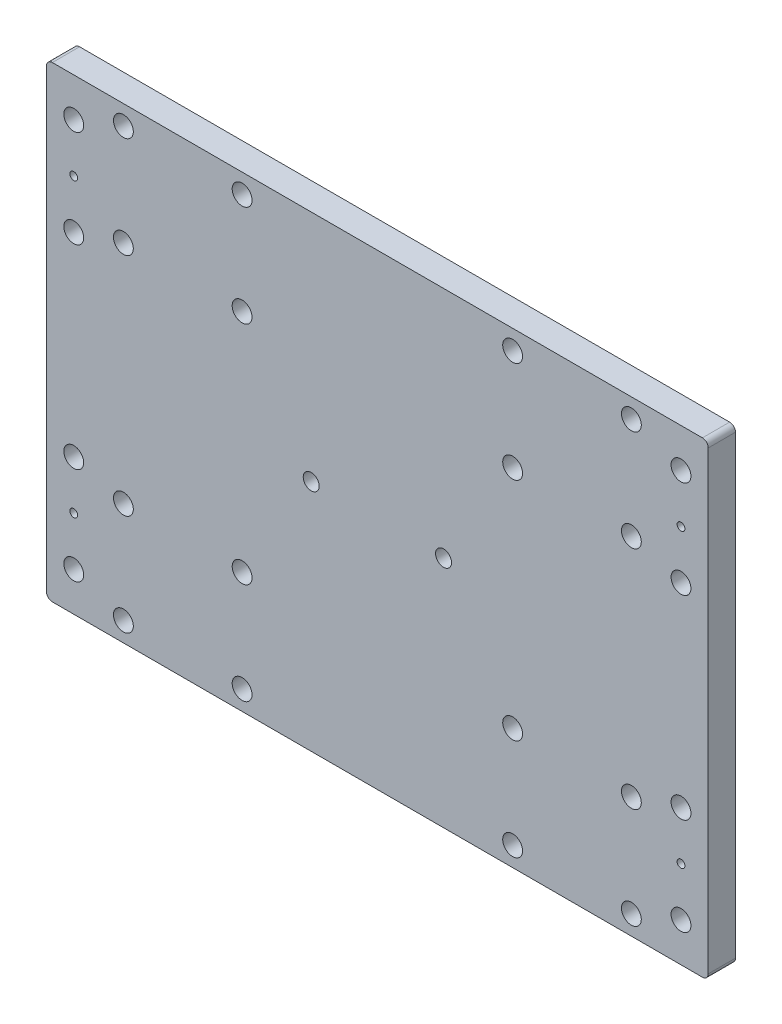
SolidWorks part; units mm, degrees
ref_plane "Front Plane" through (0, 0, 0) normal (0, 0, 1) x (1, 0, 0)
ref_plane "Top Plane" through (0, 0, 0) normal (0, 1, 0) x (1, 0, 0)
ref_plane "Right Plane" through (0, 0, 0) normal (1, 0, 0) x (0, 0, -1)
sketch "Sketch1" plane through (0, 0, 0) normal (0, 0, 1) x (1, 0, 0)
  line L1 (85, -60) -> (-85, -60)
  line L2 (85, -60) -> (85, 60)
  line L3 (85, 60) -> (-85, 60)
  line L4 (-85, -60) -> (-85, 60)
  line L5 (85, -60) -> (-85, 60) construction
  line L6 (85, 60) -> (-85, -60) construction
  point P0 (0, 0)
  dimension "D1" = 170
  dimension "D2" = 120
extrude "Boss-Extrude1" add sketch "Sketch1" along normal mid plane 7
sketch "Sketch2" plane through (0, 0, 3.5) normal (0, 0, 1) x (1, 0, 0)
  line L0 (-65.25, 71) -> (-65.25, -71) construction
  line L1 (65.25, -71) -> (65.25, 71) construction
  line L2 (-34.75, 71) -> (-34.75, -71) construction
  line L3 (34.75, -71) -> (34.75, 71) construction
  line L4 (70.6711, 55) -> (-71.3289, 55) construction
  line L5 (-71.3289, -55) -> (70.6711, -55) construction
  line L6 (70.6711, 29) -> (-71.3289, 29) construction
  line L7 (-71.3289, -29) -> (70.6711, -29) construction
  line L8 (85, 60) -> (-85, 60) construction
  line L9 (-85, -60) -> (85, -60) construction
  line L10 (-85, 60) -> (-85, -60) construction
  line L11 (85, -60) -> (85, 60) construction
  circle A0 centre (-65.25, 55) radius 2.55
  circle A1 centre (-34.75, 55) radius 2.55
  circle A2 centre (-34.75, 29) radius 2.55
  circle A3 centre (-65.25, 29) radius 2.55
  circle A4 centre (65.25, 55) radius 2.55
  circle A5 centre (65.25, 29) radius 2.55
  circle A6 centre (34.75, 29) radius 2.55
  circle A7 centre (34.75, 55) radius 2.55
  circle A8 centre (-65.25, -29) radius 2.55
  circle A9 centre (-34.75, -29) radius 2.55
  circle A10 centre (-34.75, -55) radius 2.55
  circle A11 centre (-65.25, -55) radius 2.55
  circle A12 centre (34.75, -29) radius 2.55
  circle A13 centre (65.25, -29) radius 2.55
  circle A14 centre (65.25, -55) radius 2.55
  circle A15 centre (34.75, -55) radius 2.55
  dimension "D1" = 5.1
  dimension "D2" = 5.1
  dimension "D3" = 5.1
  dimension "D4" = 5.1
  dimension "D5" = 5.1
  dimension "D6" = 5.1
  dimension "D7" = 5.1
  dimension "D8" = 5.1
  dimension "D9" = 5.1
  dimension "D10" = 5.1
  dimension "D11" = 5.1
  dimension "D12" = 5.1
  dimension "D13" = 5.1
  dimension "D14" = 5.1
  dimension "D15" = 5.1
  dimension "D16" = 5.1
  dimension "D17" = 5
  dimension "D18" = 5
  dimension "D19" = 26
  dimension "D20" = 26
  dimension "D21" = 30.5
  dimension "D22" = 30.5
  dimension "D23" = 19.75
  dimension "D24" = 19.75
extrude "Cut-Extrude1" cut sketch "Sketch2" against normal through all
sketch "Sketch4" plane through (0, 0, 3.5) normal (0, 0, 1) x (1, 0, 0)
  line L3 (-17, 0) -> (17, 0) construction
  circle A0 centre (-17, 0) radius 2.05
  circle A3 centre (17, 0) radius 2.05
  point P0 (0, 0)
  dimension "D3" = 4.1
  dimension "D4" = 4.1
  dimension "D1" = 34
extrude "Cut-Extrude3" cut sketch "Sketch4" against normal through all
fillet "Fillet1" radius 1.5 4 edges at (-85, -60, 0) (85, -60, 0) (85, 60, 0) (-85, 60, 0)
sketch "Sketch6" plane through (0, 0, 3.5) normal (0, 0, 1) x (1, 0, 0)
  line L0 (-78, -1002.1032) -> (-78, 48997.8968) construction
  line L1 (78, -1010.3548) -> (78, 48989.6452) construction
  line L2 (-85, 58.5) -> (-85, -58.5) construction
  line L3 (85, -58.5) -> (85, 58.5) construction
  line L4 (83.5, 60) -> (-83.5, 60) construction
  line L5 (-83.5, -60) -> (83.5, -60) construction
  circle A0 centre (-78, 50) radius 2.55
  circle A1 centre (-78, 37.5) radius 1
  circle A2 centre (-78, 25) radius 2.55
  circle A3 centre (-78, -25) radius 2.55
  circle A4 centre (-78, -37.5) radius 1
  circle A5 centre (-78, -50) radius 2.55
  dimension "D3" = 5.1
  dimension "D4" = 2
  dimension "D5" = 5.1
  dimension "D6" = 5.1
  dimension "D7" = 5.1
  dimension "D8" = 2
  dimension "D9" = 10
  dimension "D12" = 35
  dimension "D14" = 10
  dimension "D1" = 7
  dimension "D2" = 7
  dimension "D10" = 22.5
  dimension "D11" = 35
  dimension "D13" = 22.5
extrude "Cut-Extrude5" cut sketch "Sketch6" against normal through all
mirror "Mirror1" about plane through (0, 0, 0) normal (1, 0, 0) of "Cut-Extrude5"
equation "\"D23@Sketch2\"=5.75+14"
equation "\"D24@Sketch2\"=5.75+14"
equation "\"D4@Sketch4\"=\"D3@Sketch4\""
equation "\"D5@Sketch6\" = \"D3@Sketch6\""
equation "\"D6@Sketch6\" = \"D3@Sketch6\""
equation "\"D7@Sketch6\"=\"D3@Sketch6\""
